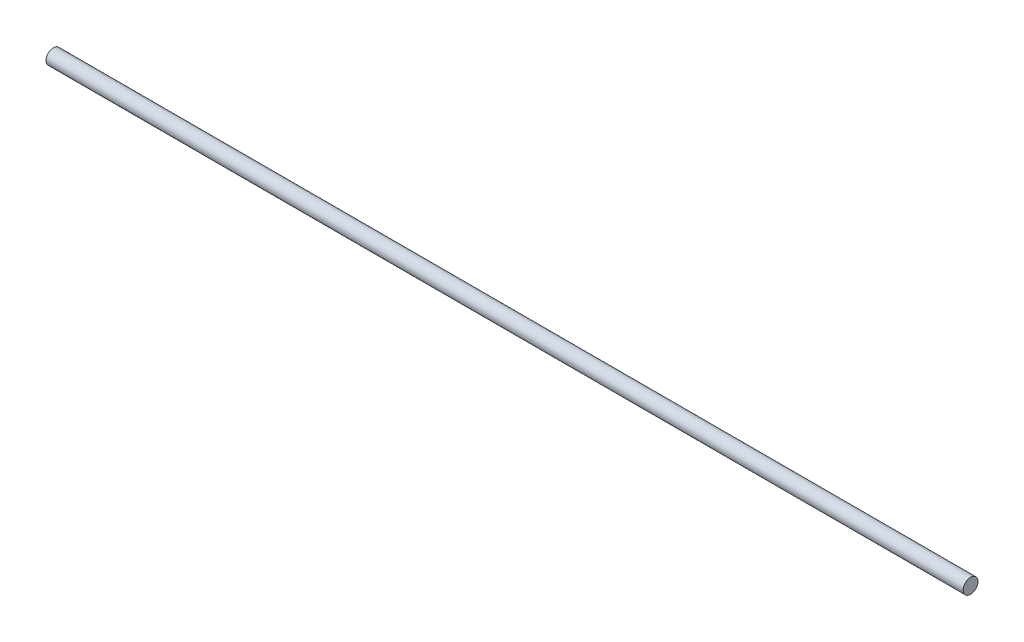
SolidWorks part; units mm, degrees
ref_plane "Front Plane" through (0, 0, 0) normal (0, 0, 1) x (1, 0, 0)
ref_plane "Top Plane" through (0, 0, 0) normal (0, 1, 0) x (1, 0, 0)
ref_plane "Right Plane" through (0, 0, 0) normal (1, 0, 0) x (0, 0, -1)
sketch "Sketch1" plane through (0, 0, 0) normal (1, 0, 0) x (0, 0, -1)
  circle A0 centre (0, 0) radius 3.175
  dimension "D1" = 6.35
extrude "Boss-Extrude1" add sketch "Sketch1" along normal blind 393.7
